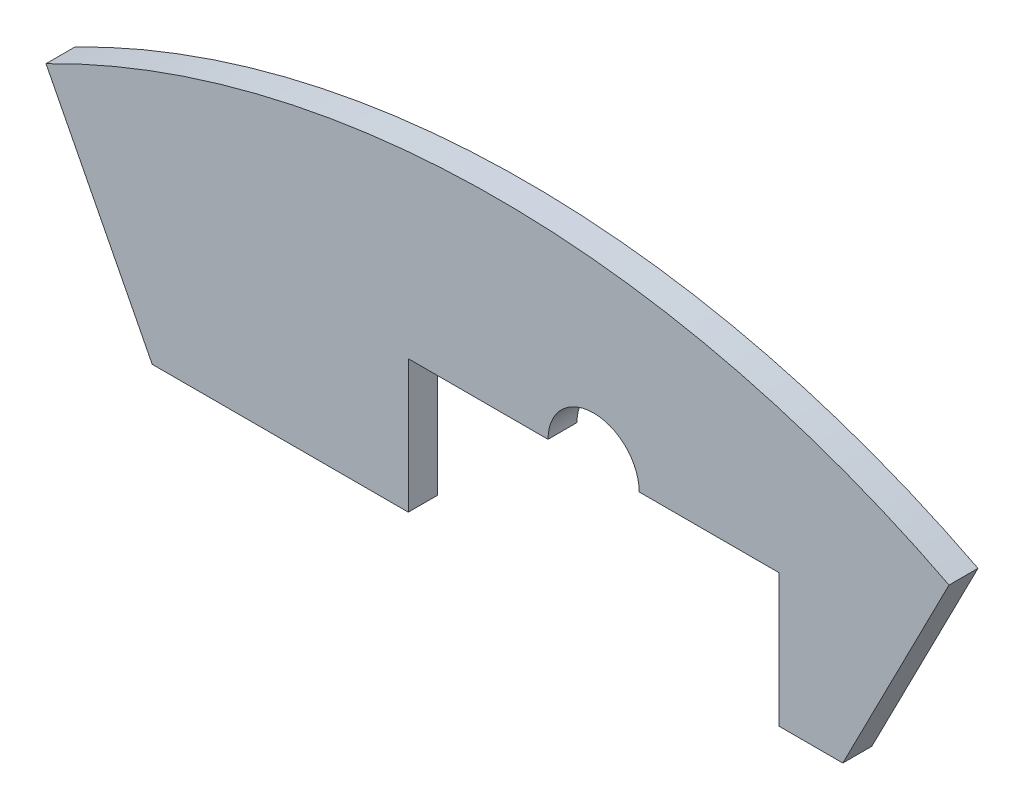
SolidWorks part; units mm, degrees
ref_plane "Front Plane" through (0, 0, 0) normal (0, 0, 1) x (1, 0, 0)
ref_plane "Top Plane" through (0, 0, 0) normal (0, 1, 0) x (1, 0, 0)
ref_plane "Right Plane" through (0, 0, 0) normal (1, 0, 0) x (0, 0, -1)
sketch "Sketch1" plane through (0, 0, 0) normal (0, 0, 1) x (1, 0, 0)
  line L0 (-49.4933, 96.5799) -> (-37.85, 73.8596)
  line L1 (-9.78, 88.4323) -> (5.535, 88.4323)
  line L2 (37.85, 73.8596) -> (49.4933, 96.5799)
  line L3 (0, 0) -> (0, 132.1946) construction
  line L4 (0, -55) -> (0, 55) construction
  line L5 (-37.85, 73.8596) -> (-9.78, 73.8596)
  line L6 (-9.78, 73.8596) -> (-9.78, 88.4323)
  line L7 (15.535, 88.4323) -> (30.85, 88.4323)
  line L8 (30.85, 88.4323) -> (30.85, 73.8596)
  line L9 (30.85, 73.8596) -> (37.85, 73.8596)
  arc A0 (5.535, 88.4323) -> (15.535, 88.4323) centre (10.535, 88.4323) cw
  arc A1 (49.4933, 96.5799) -> (-49.4933, 96.5799) centre (0, 0) ccw
  dimension "D1" = 25.53
  dimension "D3" = 28.07
  dimension "D5" = 5
  dimension "D2" = 75.7
  dimension "D4" = 7
  dimension "D6" = 40.63
  dimension "D7" = 20.315
extrude "Boss-Extrude1" add sketch "Sketch1" along normal blind 3.175
